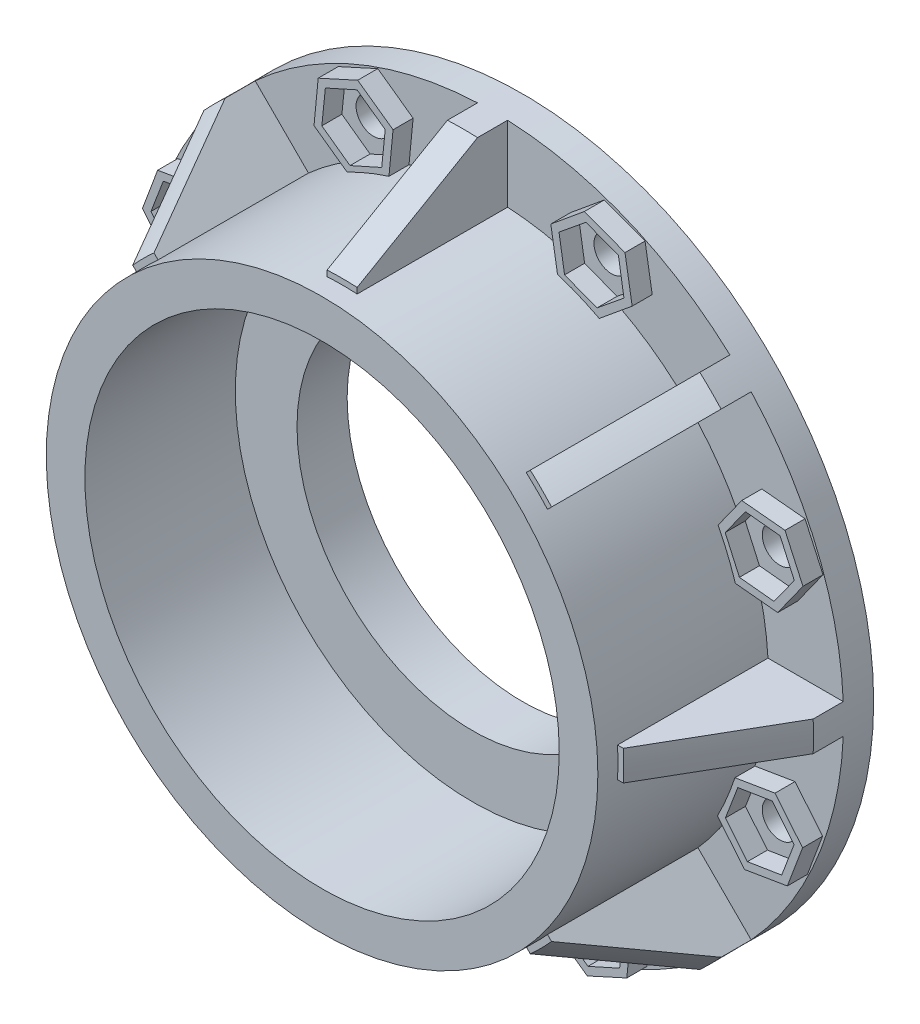
SolidWorks part; units mm, degrees
ref_plane "Front Plane" through (0, 0, 0) normal (0, 0, 1) x (1, 0, 0)
ref_plane "Top Plane" through (0, 0, 0) normal (0, 1, 0) x (1, 0, 0)
ref_plane "Right Plane" through (0, 0, 0) normal (1, 0, 0) x (0, 0, -1)
sketch "Sketch1" plane through (0, 0, 0) normal (0, 0, 1) x (1, 0, 0)
  circle A0 centre (0, 0) radius 17.5
  circle A1 centre (0, 0) radius 27.5
  dimension "D1" = 35
  dimension "D2" = 55
extrude "Boss-Extrude1" add sketch "Sketch1" along normal blind 5
sketch "Sketch2" plane through (0, 0, 5) normal (0, 0, 1) x (1, 0, 0)
  circle A0 centre (0, 0) radius 23.65
  circle A1 centre (0, 0) radius 27.5
  dimension "D1" = 47.3
extrude "Boss-Extrude2" add sketch "Sketch2" along normal blind 15
sketch "Sketch3" plane through (0, 0, 0) normal (0, 0, 1) x (1, 0, 0)
  circle A0 centre (0, 0) radius 35
  circle A1 centre (0, 0) radius 17.5
  dimension "D1" = 70
extrude "Boss-Extrude3" add sketch "Sketch3" along normal blind 3
sketch "Sketch4" plane through (0, 0, 3) normal (0, 0, 1) x (1, 0, 0)
  line L0 (0, 27.4591) -> (0, 0) construction
  line L2 (-1.5, 27.4591) -> (-1.5, 34.9678)
  line L4 (1.5, 27.4591) -> (1.5, 34.9678)
  line L5 (-1.5, 27.4591) -> (1.5, 27.4591) construction
  line L6 (-1.5, 34.9678) -> (1.5, 34.9678) construction
  circle A0 centre (0, 0) radius 27.5 construction
  circle A1 centre (0, 0) radius 35 construction
  arc A2 (-1.5, 34.9678) -> (1.5, 34.9678) centre (0, 0) cw
  arc A3 (-1.5, 27.4591) -> (1.5, 27.4591) centre (0, 0) cw
  point P14 (0, 27.4591)
  dimension "D1" = 3
extrude "Boss-Extrude4" add sketch "Sketch4" along normal blind 15
chamfer "Chamfer1" distance 12 angle 30 1 edges at (0, 35, 18) first distance on face at (0, 17.4839, 10.5)
pattern_circular "CirPattern1" count 8 every 45 about axis through (0, 0, 3) along (0, 0, 1) of "Boss-Extrude4", "Chamfer1"
sketch "Sketch5" plane through (0, 0, 3) normal (0, 0, 1) x (1, 0, 0)
  line L0 (0, 0) -> (12.5827, -30.3773) construction
  line L1 (1.5, -34.9678) -> (23.6653, -25.7867) construction
  circle A0 centre (11.8632, -28.6403) radius 1.75
  dimension "D2" = 3.5
  dimension "D1" = 31
extrude "Cut-Extrude1" cut sketch "Sketch5" against normal blind 20
sketch "Sketch7" plane through (0, 0, 3) normal (0, 0, 1) x (1, 0, 0)
  line L1 (15.0235, -27.2217) -> (12.2148, -25.1941)
  line L2 (12.2148, -25.1941) -> (9.0545, -26.6126)
  line L3 (9.0545, -26.6126) -> (8.7029, -30.0588)
  line L4 (8.7029, -30.0588) -> (11.5116, -32.0865)
  line L5 (11.5116, -32.0865) -> (14.6719, -30.6679)
  line L6 (14.6719, -30.6679) -> (15.0235, -27.2217)
  line L7 (15.8045, -26.847) -> (12.2809, -24.3303)
  line L8 (12.2809, -24.3303) -> (8.3395, -26.1236)
  line L9 (8.3395, -26.1236) -> (7.9218, -30.4335)
  line L10 (7.9218, -30.4335) -> (11.4455, -32.9502)
  line L11 (11.4455, -32.9502) -> (15.3869, -31.157)
  line L12 (15.3869, -31.157) -> (15.8045, -26.847)
  circle A0 centre (11.8632, -28.6403) radius 3 construction
  circle A1 centre (11.8632, -28.6403) radius 3.75 construction
  dimension "D1" = 6
  dimension "D2" = 7.5
extrude "Boss-Extrude5" add sketch "Sketch7" along normal blind 2
pattern_circular "CirPattern2" count 8 every 45 about axis through (0, 0, 5) along (0, 0, 1) of "Cut-Extrude1", "Boss-Extrude5"
